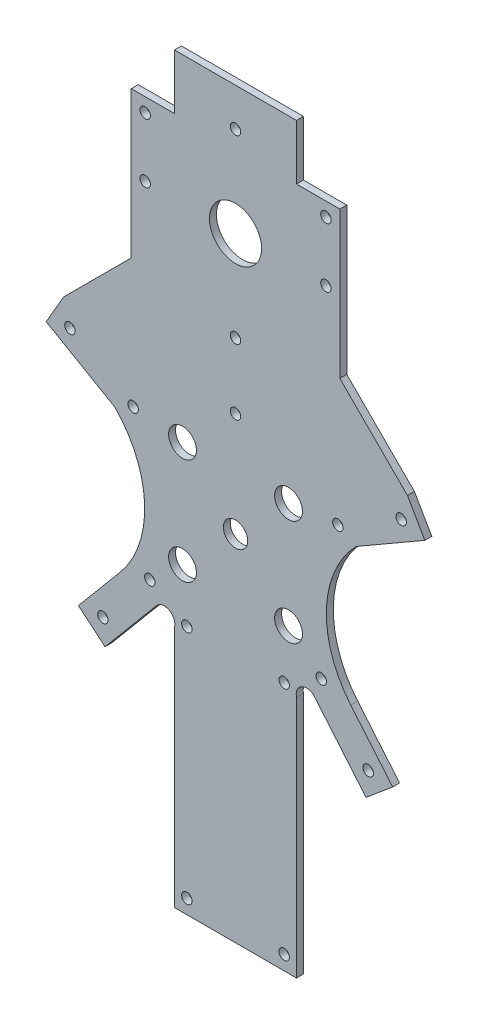
SolidWorks part; units mm, degrees
ref_plane "Alzado" through (0, 0, 0) normal (0, 0, 1) x (1, 0, 0)
ref_plane "Planta" through (0, 0, 0) normal (0, 1, 0) x (1, 0, 0)
ref_plane "Vista lateral" through (0, 0, 0) normal (1, 0, 0) x (0, 0, -1)
sketch "Croquis1" plane through (0, 0, 0) normal (0, 0, 1) x (1, 0, 0)
  line L0 (0, 0) -> (27.8544, 27.8544) construction
  line L1 (0, 0) -> (-51.9615, 30) construction
  line L2 (0, 0) -> (0, 42.4264) construction
  line L7 (-41.3657, -43.6145) -> (-24.6532, -23.6973) construction
  line L13 (-49.4615, 34.3301) -> (-54.4615, 25.6699)
  line L20 (0, 0) -> (-15.25, 0) construction
  line L32 (0, -15.25) -> (0, -101.8134) construction
  line L36 (-17.5359, -31.8134) -> (-17.5359, -101.8134)
  line L105 (17.5359, 31.8134) -> (17.5359, 111.8134)
  line L131 (17.5359, 111.8134) -> (-17.5359, 111.8134)
  line L132 (-17.5359, 31.8134) -> (-17.5359, 111.8134)
  line L160 (-14, 30) -> (-17.8891, 33.8891) construction
  line L161 (-49.4615, 34.3301) -> (-28.1732, 22.0393)
  line L221 (-54.4615, 25.6699) -> (-34.7105, 14.2666)
  line L225 (0, 0) -> (-70.3615, 0) construction
  line L226 (-33.139, -26.0317) -> (-45.1959, -40.4005)
  line L227 (-22.8364, -29.3107) -> (-37.5355, -46.8284)
  line L228 (-37.5355, -46.8284) -> (-45.1959, -40.4005)
  line L229 (17.5359, -31.8134) -> (17.5359, -101.8134)
  line L230 (22.8364, -29.3107) -> (37.5355, -46.8284)
  line L231 (37.5355, -46.8284) -> (45.1959, -40.4005)
  line L232 (33.139, -26.0317) -> (45.1959, -40.4005)
  line L233 (54.4615, 25.6699) -> (34.7105, 14.2666)
  line L234 (49.4615, 34.3301) -> (54.4615, 25.6699)
  line L235 (49.4615, 34.3301) -> (28.1732, 22.0393)
  line L236 (17.5359, -101.8134) -> (-17.5359, -101.8134)
  circle A0 centre (-15.25, 15.25) radius 4
  circle A1 centre (-29.4449, 17) radius 1.5
  circle A2 centre (-47.6314, 27.5) radius 1.5
  circle A12 centre (-15.25, -15.25) radius 4
  circle A13 centre (-24.6532, -23.6973) radius 1.5
  circle A14 centre (-38.1518, -39.7843) radius 1.5
  circle A18 centre (0, 0) radius 3.5
  circle A21 centre (-14, 30) radius 1.5 construction
  arc A141 (-22.8364, -29.3107) -> (-17.5359, -31.8134) centre (-20.4597, -31.1414) cw
  circle A142 centre (14, 30) radius 1.5 construction
  circle A144 centre (-14, -30) radius 1.5
  circle A199 centre (0, 30) radius 1.5
  circle A201 centre (-14, -97.6883) radius 1.5
  arc A203 (-17.5359, 31.8134) -> (-28.1732, 22.0393) centre (-25.7369, 30.0632) cw
  arc A204 (-34.7105, 14.2666) -> (-33.139, -26.0317) centre (-56.1204, -6.7481) cw
  circle A205 centre (14, -97.6883) radius 1.5
  circle A206 centre (14, -30) radius 1.5
  circle A207 centre (47.6314, 27.5) radius 1.5
  circle A208 centre (29.4449, 17) radius 1.5
  circle A209 centre (15.25, 15.25) radius 4
  circle A210 centre (15.25, -15.25) radius 4
  circle A211 centre (24.6532, -23.6973) radius 1.5
  arc A212 (22.8364, -29.3107) -> (17.5359, -31.8134) centre (20.4597, -31.1414) ccw
  circle A213 centre (38.1518, -39.7843) radius 1.5
  arc A214 (34.7105, 14.2666) -> (33.139, -26.0317) centre (56.1204, -6.7481) ccw
  arc A215 (17.5359, 31.8134) -> (28.1732, 22.0393) centre (25.7369, 30.0632) ccw
  point P260 (-7.0711, 0)
  dimension "D2" = 8
  dimension "D4" = 30
  dimension "D8" = 14.75
  dimension "D10" = 3
  dimension "D11" = 3
  dimension "D13" = 40
  dimension "D15" = 35.0718
  dimension "D16" = 14
  dimension "D18" = 21
  dimension "D24" = 3
  dimension "D27" = 7
  dimension "D28" = 3
  dimension "D6" = 30.5
  dimension "D25" = 3
  dimension "D3" = 60
  dimension "D5" = 21
  dimension "D7" = 10
  dimension "D9" = 5
  dimension "D12" = 80
  dimension "D14" = 30
  dimension "D17" = 35.0718
  dimension "D20" = 5
  dimension "D21" = 10
  dimension "D22" = 60
  dimension "D23" = 5.5
  dimension "D30" = 30.5
extrude "Base" add sketch "Croquis1" along normal blind 2
sketch "Croquis2" plane through (0, 0, 2) normal (0, 0, 1) x (1, 0, 0)
  line L0 (28.1732, 22.0393) -> (49.4615, 34.3301)
  line L1 (30, 95.9619) -> (-30, 95.9619)
  line L2 (30, 95.9619) -> (30, 53.7917)
  line L3 (17.5359, 61.6883) -> (-17.5359, 61.6883)
  line L7 (49.4615, 34.3301) -> (30, 53.7917)
  line L8 (-30, 95.9619) -> (-30, 53.7917)
  line L9 (-49.4615, 34.3301) -> (-30, 53.7917)
  line L10 (0, 0) -> (0, 61.6883) construction
  line L12 (-28.1732, 22.0393) -> (-49.4615, 34.3301)
  line L13 (-17.5359, 61.6883) -> (-17.5359, 31.8134)
  line L16 (17.5359, 61.6883) -> (17.5359, 31.8134)
  arc A2 (-28.1732, 22.0393) -> (-17.5359, 31.8134) centre (-25.7369, 30.0632) ccw
  arc A3 (17.5359, 31.8134) -> (28.1732, 22.0393) centre (25.7369, 30.0632) ccw
  point P7 (0, 95.9619)
  dimension "D1" = 61.6883
  dimension "D2" = 60
extrude "BaseGimbal" add sketch "Croquis2" against normal up to vertex (2 mm away) up to point (-17.5359, 31.8134, 0)
sketch "Croquis3" plane through (0, 0, 2) normal (0, 0, 1) x (1, 0, 0)
  line L1 (-30, 95.9619) -> (-30, 53.7917) construction
  line L2 (30, 53.7917) -> (30, 95.9619) construction
  line L8 (17.5359, 111.8134) -> (-17.5359, 111.8134) construction
  line L9 (0, 74.8768) -> (30, 74.8768) construction
  line L10 (30, 53.7917) -> (30, 95.9619) construction
  line L11 (30, 95.9619) -> (17.5359, 95.9619) construction
  line L16 (-17.5359, 95.9619) -> (-30, 95.9619) construction
  circle A4 centre (0, 74.8768) radius 7.5
  circle A5 centre (26, 91.9619) radius 1.5
  circle A6 centre (-26, 91.9619) radius 1.5
  circle A7 centre (26, 74.8768) radius 1.5
  circle A11 centre (0, 74.8768) radius 26 construction
  circle A12 centre (0, 48.8768) radius 1.5
  circle A13 centre (-26, 74.8768) radius 1.5
  circle A14 centre (0, 100.8768) radius 1.5
  point P6 (0, 74.8768)
  point P22 (0, 74.8768)
  point P39 (0, 111.8134)
  dimension "D2" = 4
  dimension "D5" = 15
  dimension "D6" = 3
  dimension "D7" = 3
  dimension "D8" = 4
  dimension "D9" = 4
  dimension "D4" = 52
  dimension "D3" = 4
  dimension "D14" = 4
extrude "CortesBaseGimbal" cut sketch "Croquis3" against normal up to vertex (2 mm away) up to point (-30, 53.7917, 0)
fillet "Redondeo1" radius 3 rebuild error yes
fillet "Redondeo2" radius 10 rebuild error yes
fillet "Redondeo3" radius 2 rebuild error yes
